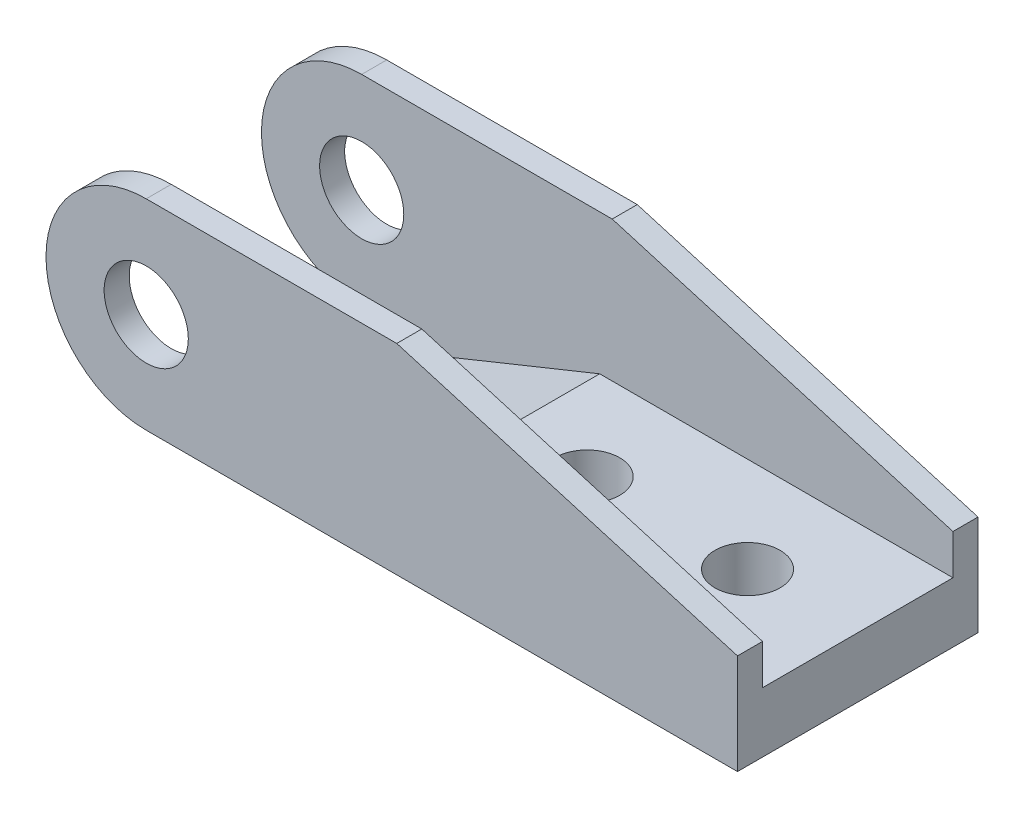
SolidWorks part; units mm, degrees
ref_plane "Alzado" through (0, 0, 0) normal (0, 0, 1) x (1, 0, 0)
ref_plane "Planta" through (0, 0, 0) normal (0, 1, 0) x (1, 0, 0)
ref_plane "Vista lateral" through (0, 0, 0) normal (1, 0, 0) x (0, 0, -1)
sketch "Croquis1" plane through (0, 0, 0) normal (0, 1, 0) x (1, 0, 0)
  line L1 (-17.25, -6) -> (17.25, -6)
  line L2 (-17.25, -6) -> (-17.25, 6)
  line L3 (-17.25, 6) -> (17.25, 6)
  line L4 (17.25, -6) -> (17.25, 6)
  line L5 (-17.25, -6) -> (17.25, 6) construction
  line L6 (-17.25, 6) -> (17.25, -6) construction
  point P0 (0, 0)
  dimension "D1" = 12
  dimension "D2" = 34.5
extrude "Saliente-Extruir1" add sketch "Croquis1" along normal blind 10
fillet "Redondeo1" radius 5 2 edges at (-17.25, 10, 0) (-17.25, 0, 0)
sketch "Croquis8" plane through (0, 10, 0) normal (0, 1, 0) x (1, 0, 0)
  line L0 (17.25, -6) -> (17.25, 6) construction
  line L1 (17.25, 4.75) -> (-17.25, 4.75)
  line L2 (17.25, 4.75) -> (17.25, -4.75)
  line L3 (17.25, -4.75) -> (-17.25, -4.75)
  line L4 (-17.25, 4.75) -> (-17.25, -4.75)
  line L5 (-17.25, 6) -> (-17.25, -6) construction
  line L6 (0, 0) -> (17.25, 0) construction
  dimension "D1" = 9.5
extrude "Cortar-Extruir6" cut sketch "Croquis8" against normal blind 7
sketch "Croquis9" plane through (0, 0, 0) normal (0, -1, 0) x (1, 0, 0)
  line L0 (-12.25, 4.75) -> (17.25, 4.75) construction
  line L1 (-18.5371, 4.75) -> (-7.8, 4.75)
  line L2 (-18.5371, 4.75) -> (-18.5371, -4.75)
  line L3 (-18.5371, -4.75) -> (-7.8, -4.75)
  line L4 (-7.8, 4.75) -> (-7.8, -4.75)
  line L5 (17.25, -4.75) -> (-12.25, -4.75) construction
  line L6 (17.25, 6) -> (17.25, -6) construction
  dimension "D1" = 25.05
extrude "Cortar-Extruir7" cut sketch "Croquis9" against normal through all
chamfer "Chaflán1" distance 3 angle 68 1 edges at (-7.8, 3, 0) first distance on face at (-7.8, 1.5, 0)
sketch "Croquis10" plane through (0, 0, 6) normal (0, 0, 1) x (1, 0, 0)
  line L0 (0.25, 10) -> (17.25, 5)
  line L1 (-12.25, 10) -> (17.25, 10) construction
  line L3 (17.25, 5) -> (17.25, 10)
  line L4 (17.25, 10) -> (0.25, 10)
  line L7 (-12.25, 0) -> (17.25, 0) construction
  dimension "D1" = 5
  dimension "D2" = 17
extrude "Cortar-Extruir8" cut sketch "Croquis10" against normal through all
sketch "Croquis11" plane through (0, 0, 6) normal (0, 0, 1) x (1, 0, 0)
  circle A0 centre (-12.25, 5) radius 2.1
  arc A1 (-12.25, 10) -> (-17.25, 5) centre (-12.25, 5) ccw construction
  dimension "D1" = 4.2
extrude "Cortar-Extruir9" cut sketch "Croquis11" against normal through all
sketch "Croquis12" plane through (0, 3, 0) normal (0, 1, 0) x (1, 0, 0)
  line L0 (11.75, 0) -> (17.25, 0) construction
  line L1 (17.25, -4.75) -> (17.25, 4.75) construction
  circle A0 centre (3.75, 0) radius 1.625
  circle A1 centre (11.75, 0) radius 1.625
  dimension "D2" = 3.25
  dimension "D1" = 8
  dimension "D3" = 5.5
extrude "Cortar-Extruir10" cut sketch "Croquis12" against normal through all
